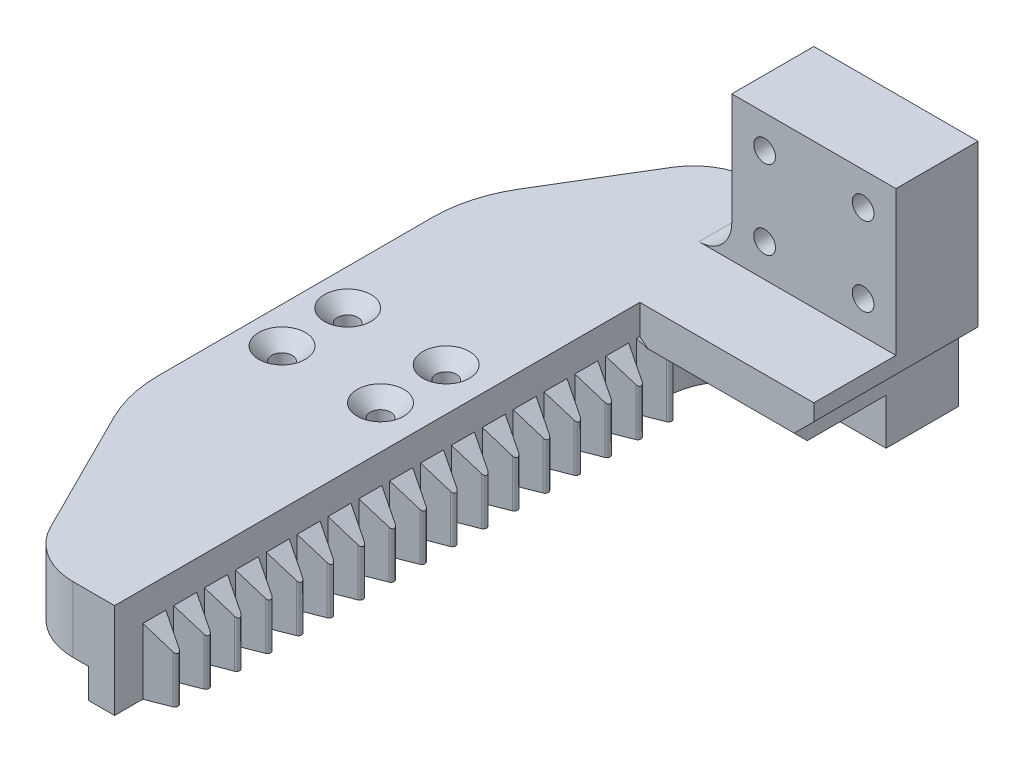
SolidWorks part; units mm, degrees
ref_plane "Front Plane" through (0, 0, 0) normal (0, 0, 1) x (1, 0, 0)
ref_plane "Top Plane" through (0, 0, 0) normal (0, 1, 0) x (1, 0, 0)
ref_plane "Right Plane" through (0, 0, 0) normal (1, 0, 0) x (0, 0, -1)
sketch "Sketch1" plane through (0, 0, 0) normal (0, 1, 0) x (1, 0, 0)
  line L0 (-53.5, -24) -> (-39, 0)
  line L1 (0, 0) -> (-39, 0)
  line L2 (0, 0) -> (0, -105)
  line L3 (0, -105) -> (-39, -105)
  line L4 (-53.5, -24) -> (-53.5, -76)
  line L5 (-53.5, -76) -> (-39, -105)
  dimension "D1" = 105
  dimension "D2" = 53.5
  dimension "D3" = 39
  dimension "D4" = 52
  dimension "D5" = 24
  dimension "D6" = 39
extrude "Boss-Extrude1" add sketch "Sketch1" along normal blind 14.5
sketch "Sketch2" plane through (0, 14.5, 0) normal (0, 1, 0) x (1, 0, 0)
  line L0 (0, -105) -> (0, 0) construction
  line L1 (0, -25) -> (-26.5, -25)
  line L2 (0, -25) -> (0, -105)
  line L3 (0, -105) -> (-26.5, -105)
  line L4 (-26.5, -25) -> (-26.5, -105)
  line L5 (-39, -105) -> (0, -105) construction
  dimension "D1" = 26.5
  dimension "D2" = 25
extrude "Cut-Extrude1" cut sketch "Sketch2" against normal blind 15
sketch "Sketch4" plane through (0, 0, 0) normal (0, -1, 0) x (1, 0, 0)
  line L0 (0, 25) -> (0, 0) construction
  line L1 (0, 11) -> (-26.5, 11)
  line L2 (0, 11) -> (0, 25)
  line L3 (0, 25) -> (-26.5, 25)
  line L4 (-26.5, 11) -> (-26.5, 25)
  line L5 (0, 0) -> (-39, 0) construction
  dimension "D1" = 11
extrude "Cut-Extrude2" cut sketch "Sketch4" against normal blind 7
fillet "Fillet1" radius 10 1 edges at (-26.5, 3.5, 11)
sketch "Sketch5" plane through (0, 0, 0) normal (0, 0, -1) x (-1, 0, 0)
  line L1 (0, 0) -> (3, 0)
  line L2 (0, 0) -> (0, 12)
  line L3 (0, 12) -> (3, 12)
  line L4 (3, 0) -> (3, 12)
  dimension "D1" = 3
  dimension "D2" = 12
extrude "Cut-Extrude3" cut sketch "Sketch5" against normal blind 29
chamfer "Chamfer1" distance 3 angle 45 1 edges at (-3, 12, 12.5)
chamfer "Chamfer2" distance 2 angle 45 1 edges at (-14.75, 7, 25)
sketch "Sketch6" plane through (0, 0, 0) normal (0, -1, 0) x (1, 0, 0)
  line L1 (-26.5, 21) -> (-26.5, 105) construction
  line L4 (-26.5, 25.5) -> (-26.5, 22)
  line L5 (-26.5, 22) -> (-23.1983, 23.284)
  line L7 (-26.5, 25.5) -> (-23.1983, 24.216)
  arc A0 (-23.1983, 23.284) -> (-23.1983, 24.216) centre (-23.3795, 23.75) ccw
  dimension "D4" = 1
  dimension "D1" = 22
  dimension "D2" = 3.5
  dimension "D5" = 1.75
extrude "Boss-Extrude2" add sketch "Sketch6" against normal blind 10
pattern_linear "LPattern1" count 17 spacing 4.7 along (0, 0, 1) of "Boss-Extrude2"
sketch "Sketch7" plane through (0, 0, 25) normal (0, 0, 1) x (1, 0, 0)
  line L0 (-26.5, 10) -> (-22.8795, 7)
  line L1 (-22.8795, 0) -> (-22.8795, 10) construction
  line L2 (-26.5, 7) -> (-16.5, 7) construction
  line L3 (-22.8795, 7) -> (-22.8795, 10)
  line L4 (-22.8795, 10) -> (-26.5, 10)
extrude "Cut-Extrude4" cut sketch "Sketch7" along normal blind 76
sketch "Sketch8" plane through (0, 0, 0) normal (0, -1, 0) x (1, 0, 0)
  line L0 (-3, 0) -> (-39, 0) construction
  line L1 (-30.5, 0) -> (-63.9545, 0)
  line L2 (-30.5, 0) -> (-30.5, 107.0376)
  line L3 (-30.5, 107.0376) -> (-63.9545, 107.0376)
  line L4 (-63.9545, 0) -> (-63.9545, 107.0376)
  line L5 (-53.5, 24) -> (-53.5, 76) construction
  dimension "D1" = 23
extrude "Cut-Extrude5" cut sketch "Sketch8" against normal blind 4.5
fillet "Fillet2" radius 20 2 edges at (-53.5, 9.5, 76) (-53.5, 9.5, 24)
fillet "Fillet3" radius 10 2 edges at (-39, 9.5, 105) (-39, 9.5, 0)
sketch "Sketch9" plane through (0, 14.5, 0) normal (0, 1, 0) x (1, 0, 0)
  line L1 (0, 0) -> (-25, 0)
  line L2 (0, 0) -> (0, -12.5)
  line L3 (0, -12.5) -> (-25, -12.5)
  line L4 (-25, 0) -> (-25, -12.5)
  dimension "D1" = 25
  dimension "D2" = 12.5
extrude "Boss-Extrude3" add sketch "Sketch9" along normal blind 22
fillet "Fillet4" radius 5 1 edges at (-25, 14.5, 6.25)
sketch "Sketch10" plane through (0, 0, 12.5) normal (0, 0, 1) x (1, 0, 0)
  line L0 (-25, 36.5) -> (0, 36.5) construction
  line L1 (0, 36.5) -> (0, 14.5) construction
  line L2 (-25, 36.5) -> (-25, 19.5) construction
  circle A0 centre (-20, 31.5) radius 1.65
  circle A1 centre (-5, 31.5) radius 1.65
  circle A2 centre (-5, 19.5) radius 1.65
  circle A3 centre (-20, 19.5064) radius 1.65
  dimension "D8" = 3.3
  dimension "D9" = 3.3
  dimension "D10" = 3.3
  dimension "D11" = 3.3
  dimension "D1" = 5
  dimension "D2" = 5
  dimension "D3" = 5
  dimension "D4" = 5
  dimension "D5" = 5
  dimension "D6" = 5
  dimension "D7" = 12
extrude "Cut-Extrude6" cut sketch "Sketch10" against normal blind 22
sketch "Sketch12" plane through (0, 14.5, 0) normal (0, 1, 0) x (1, 0, 0)
  line L0 (0, 0) -> (-25, 0) construction
  line L1 (-53.5, -29.5726) -> (-53.5, -71.2786) construction
  circle A0 centre (-48, -48) radius 1.55
  circle A1 centre (-33, -48) radius 1.55
  circle A2 centre (-48, -58) radius 1.55
  circle A3 centre (-33, -58) radius 1.55
  dimension "D5" = 3.1
  dimension "D6" = 3.1
  dimension "D7" = 3.1
  dimension "D8" = 3.1
  dimension "D1" = 48
  dimension "D2" = 48
  dimension "D3" = 15
  dimension "D4" = 5.5
  dimension "D9" = 15
  dimension "D10" = 10
  dimension "D11" = 10
  dimension "D12" = 33
extrude "Cut-Extrude7" cut sketch "Sketch12" against normal blind 22
chamfer "Chamfer3" distance 2 angle 45 4 edges at (-48, 14.5, 59.55) (-33, 14.5, 59.55) (-33, 14.5, 49.55) (-48, 14.5, 49.55)
sketch "Sketch13" plane through (0, 4.5, 0) normal (0, -1, 0) x (1, 0, 0)
  line L0 (-53.5, 71.2786) -> (-53.5, 29.5726) construction
  line L1 (-53.5, 69) -> (-30.5, 69)
  line L2 (-53.5, 69) -> (-53.5, 37)
  line L3 (-53.5, 37) -> (-30.5, 37)
  line L4 (-30.5, 69) -> (-30.5, 37)
  line L5 (-30.5, 0) -> (-30.5, 105) construction
  circle A0 centre (-48, 58) radius 1.55 construction
  circle A1 centre (-48, 48) radius 1.55 construction
  dimension "D1" = 11
  dimension "D2" = 11
extrude "Cut-Extrude8" cut sketch "Sketch13" against normal blind 3
fillet "Fillet5" radius 5 1 edges at (-30.5, 2.25, 0)
sketch "Sketch14" plane through (0, 4.5, 0) normal (0, -1, 0) x (1, 0, 0)
  line L0 (-30.5, 5) -> (-30.5, 105) construction
  line L1 (-30.5, 20) -> (-34.5, 20)
  line L2 (-30.5, 20) -> (-30.5, 30)
  line L3 (-30.5, 30) -> (-34.5, 30)
  line L4 (-34.5, 20) -> (-34.5, 30)
  line L5 (-33.3583, 0) -> (-25.5, 0) construction
  dimension "D1" = 20
  dimension "D2" = 4
  dimension "D3" = 10
extrude "Boss-Extrude4" add sketch "Sketch14" along normal blind 4.5
chamfer "Chamfer4" distance 2 angle 45 1 edges at (-32.5, 0, 30)
